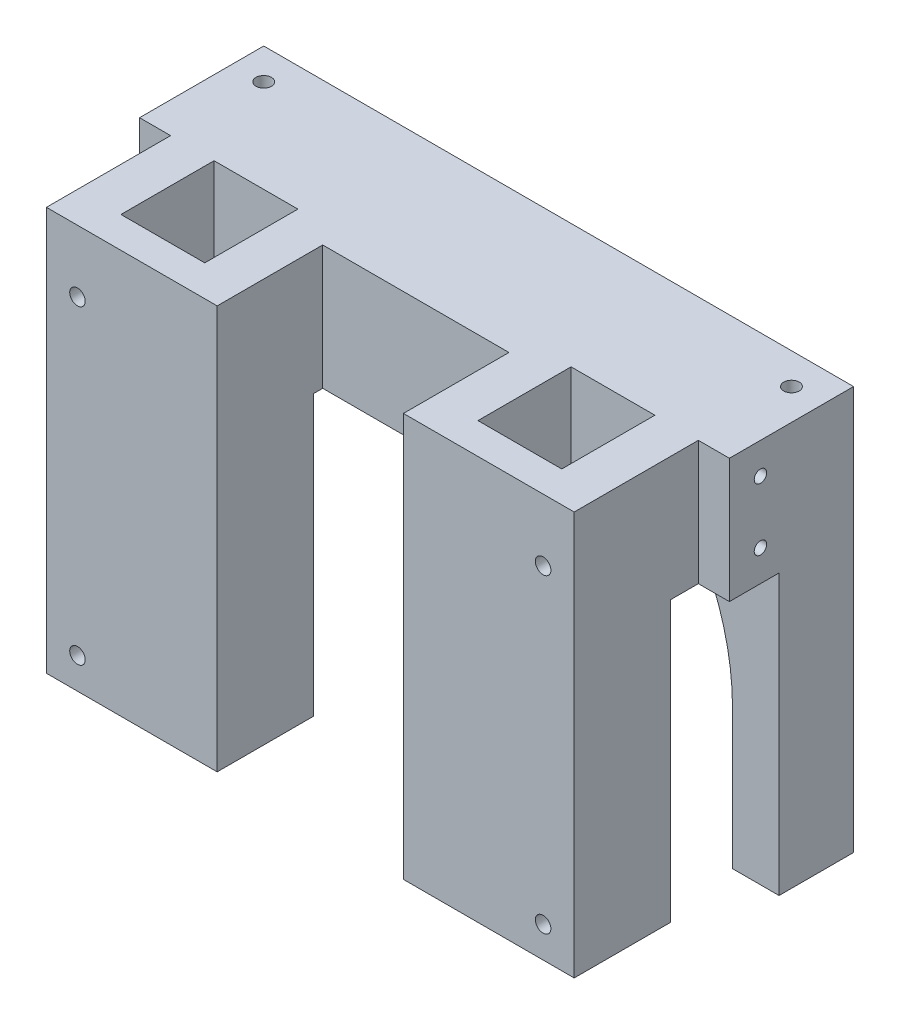
SolidWorks part; units mm, degrees
ref_plane "Plan de face" through (0, 0, 0) normal (0, 0, 1) x (1, 0, 0)
ref_plane "Plan de dessus" through (0, 0, 0) normal (0, 1, 0) x (1, 0, 0)
ref_plane "Plan de droite" through (0, 0, 0) normal (1, 0, 0) x (0, 0, -1)
sketch "Esquisse1" plane through (0, 0, 0) normal (0, 0, 1) x (1, 0, 0)
  line L1 (-47.5, 32.5) -> (47.5, 32.5)
  line L2 (-47.5, 32.5) -> (-47.5, -32.5)
  line L3 (-47.5, -32.5) -> (47.5, -32.5)
  line L4 (47.5, 32.5) -> (47.5, -32.5)
  point P4 (0, 32.5)
  point P5 (0, -32.5)
  point P6 (47.5, 0)
  point P7 (-47.5, 0)
  dimension "D1" = 95
  dimension "D2" = 65
extrude "Boss.-Extru.1" add sketch "Esquisse1" along normal blind 40
ref_plane "Plan1" through (0, -10, 0) normal (0, 1, 0) x (1, 0, 0)
sketch "Esquisse3" plane through (0, 0, 0) normal (0, 0, -1) x (-1, 0, 0)
  line L0 (22, -10) -> (-22, -10) construction
  circle A0 centre (0, -10) radius 40
  dimension "D1" = 80
extrude "Enlèv. mat.-Extru.1" cut sketch "Esquisse3" against normal blind 12
ref_plane "Plan2" through (-47.5, 32.5, 0) normal (0, 0, -1) x (-1, 0, 0)
sketch "Esquisse5" plane through (0, 32.5, 0) normal (0, 1, 0) x (1, 0, 0)
  line L1 (-42.5, -20) -> (-47.5, -20)
  line L2 (-42.5, -20) -> (-42.5, -40)
  line L3 (-42.5, -40) -> (-47.5, -40)
  line L4 (-47.5, -20) -> (-47.5, -40)
  dimension "D1" = 5
  dimension "D2" = 20
extrude "Enlèv. mat.-Extru.2" cut sketch "Esquisse5" against normal through all
sketch "Esquisse6" plane through (0, 32.5, 0) normal (0, 1, 0) x (1, 0, 0)
  line L0 (47.5, -40) -> (47.5, 0) construction
  line L1 (47.5, -20) -> (42.5, -20)
  line L2 (47.5, -20) -> (47.5, -40)
  line L3 (47.5, -40) -> (42.5, -40)
  line L4 (42.5, -20) -> (42.5, -40)
  line L5 (47.5, -40) -> (-42.5, -40) construction
  line L6 (-42.5, -20) -> (-47.5, -20) construction
  dimension "D1" = 5
extrude "Enlèv. mat.-Extru.3" cut sketch "Esquisse6" against normal through all
sketch "Esquisse7" plane through (0, 0, 0) normal (0, 0, -1) x (-1, 0, 0)
  line L0 (22, -10) -> (-22, -10) construction
  line L1 (-40, -10) -> (40, -10)
  line L2 (-40, -10) -> (-40, -32.5)
  line L3 (-40, -32.5) -> (40, -32.5)
  line L4 (40, -10) -> (40, -32.5)
  line L5 (47.5, -32.5) -> (33.0719, -32.5) construction
  arc A0 (33.0719, -32.5) -> (-33.0719, -32.5) centre (0, -10) ccw construction
  arc A1 (33.0719, -32.5) -> (-33.0719, -32.5) centre (0, -10) ccw construction
extrude "Enlèv. mat.-Extru.4" cut sketch "Esquisse7" against normal up to surface (12 mm away) up to face at (0, -1.25, 12)
sketch "Esquisse8" plane through (0, -32.5, 0) normal (0, -1, 0) x (1, 0, 0)
  line L0 (40, 12) -> (-40, 12) construction
  line L1 (-47.5, 24.5) -> (47.5, 24.5)
  line L2 (-47.5, 24.5) -> (-47.5, 12)
  line L3 (-47.5, 12) -> (47.5, 12)
  line L4 (47.5, 24.5) -> (47.5, 12)
  line L5 (-47.5, 20) -> (-47.5, 0) construction
  line L6 (47.5, 20) -> (47.5, 0) construction
  line L7 (-42.5, 40) -> (42.5, 40) construction
  dimension "D1" = 15.5
extrude "Enlèv. mat.-Extru.5" cut sketch "Esquisse8" against normal blind 45
sketch "Esquisse10" plane through (0, 0, 40) normal (0, 0, 1) x (1, 0, 0)
  line L0 (-42.5, -32.5) -> (42.5, -32.5) construction
  line L1 (-15, 32.5) -> (15, 32.5)
  line L2 (-15, 32.5) -> (-15, -32.5)
  line L3 (-15, -32.5) -> (15, -32.5)
  line L4 (15, 32.5) -> (15, -32.5)
  line L5 (42.5, 32.5) -> (-42.5, 32.5) construction
  point P6 (0, 32.5)
  dimension "D1" = 30
extrude "Enlèv. mat.-Extru.6" cut sketch "Esquisse10" against normal blind 17
sketch "Esquisse11" plane through (0, 32.5, 0) normal (0, 1, 0) x (1, 0, 0)
  line L0 (-15, -40) -> (-42.5, -40) construction
  line L1 (-35.5, -35) -> (-22, -35)
  line L2 (-35.5, -35) -> (-35.5, -20)
  line L3 (-35.5, -20) -> (-22, -20)
  line L4 (-22, -35) -> (-22, -20)
  line L5 (-42.5, -40) -> (-42.5, -20) construction
  line L6 (-15, -23) -> (-15, -40) construction
  line L10 (-42.5, -20) -> (-47.5, -20) construction
  dimension "D1" = 5
  dimension "D2" = 7
  dimension "D3" = 7
extrude "Enlèv. mat.-Extru.7" cut sketch "Esquisse11" against normal through all
sketch "Esquisse12" plane through (0, 32.5, 0) normal (0, 1, 0) x (1, 0, 0)
  line L0 (-35.5, -35) -> (-22, -35) construction
  line L1 (22, -20) -> (35.5, -20)
  line L2 (22, -20) -> (22, -35)
  line L3 (22, -35) -> (35.5, -35)
  line L4 (35.5, -20) -> (35.5, -35)
  line L5 (-22, -20) -> (-35.5, -20) construction
  line L6 (15, -23) -> (15, -40) construction
  line L7 (42.5, -20) -> (42.5, -40) construction
  dimension "D1" = 7
  dimension "D2" = 7
extrude "Enlèv. mat.-Extru.8" cut sketch "Esquisse12" against normal through all
sketch "Esquisse14" plane through (-47.5, 0, 0) normal (-1, 0, 0) x (0, 0, 1)
  line L0 (20, 12.5) -> (20, 32.5) construction
  line L2 (20, 32.5) -> (0, 32.5) construction
  circle A0 centre (15, 27.5) radius 1
  circle A1 centre (15, 17.5) radius 1
  dimension "D1" = 2
  dimension "D2" = 2
  dimension "D3" = 5
  dimension "D4" = 5
  dimension "D5" = 10
extrude "Enlèv. mat.-Extru.9" cut sketch "Esquisse14" against normal through all
sketch "Esquisse15" plane through (0, 0, 40) normal (0, 0, 1) x (1, 0, 0)
  line L0 (-15, 32.5) -> (-42.5, 32.5) construction
  line L2 (-42.5, -32.5) -> (-42.5, 32.5) construction
  line L3 (42.5, 12.5) -> (42.5, 32.5) construction
  line L4 (-42.5, -32.5) -> (-15, -32.5) construction
  circle A0 centre (-37.5, 22.5) radius 1.25
  circle A1 centre (37.5, 22.5) radius 1.25
  circle A2 centre (-37.5, -27.5) radius 1.25
  circle A3 centre (37.5, -27.5) radius 1.25
  dimension "D1" = 2.5
  dimension "D2" = 2.5
  dimension "D7" = 2.5
  dimension "D9" = 2.5
  dimension "D3" = 10
  dimension "D5" = 5
  dimension "D6" = 5
  dimension "D8" = 5
extrude "Enlèv. mat.-Extru.10" cut sketch "Esquisse15" against normal through all
sketch "Esquisse16" plane through (0, -32.5, 0) normal (0, -1, 0) x (1, 0, 0)
  line L0 (47.5, 12) -> (47.5, 0) construction
  line L1 (40, 0) -> (47.5, 0) construction
  line L2 (-47.5, 12) -> (-47.5, 0) construction
  circle A0 centre (42.5, 5) radius 1.25
  circle A1 centre (-42.5, 5) radius 1.25
  point P8 (-47.5, 6)
  dimension "D1" = 2.5
  dimension "D4" = 2.5
  dimension "D2" = 5
  dimension "D3" = 5
  dimension "D5" = 5
extrude "Enlèv. mat.-Extru.11" cut sketch "Esquisse16" against normal through all
